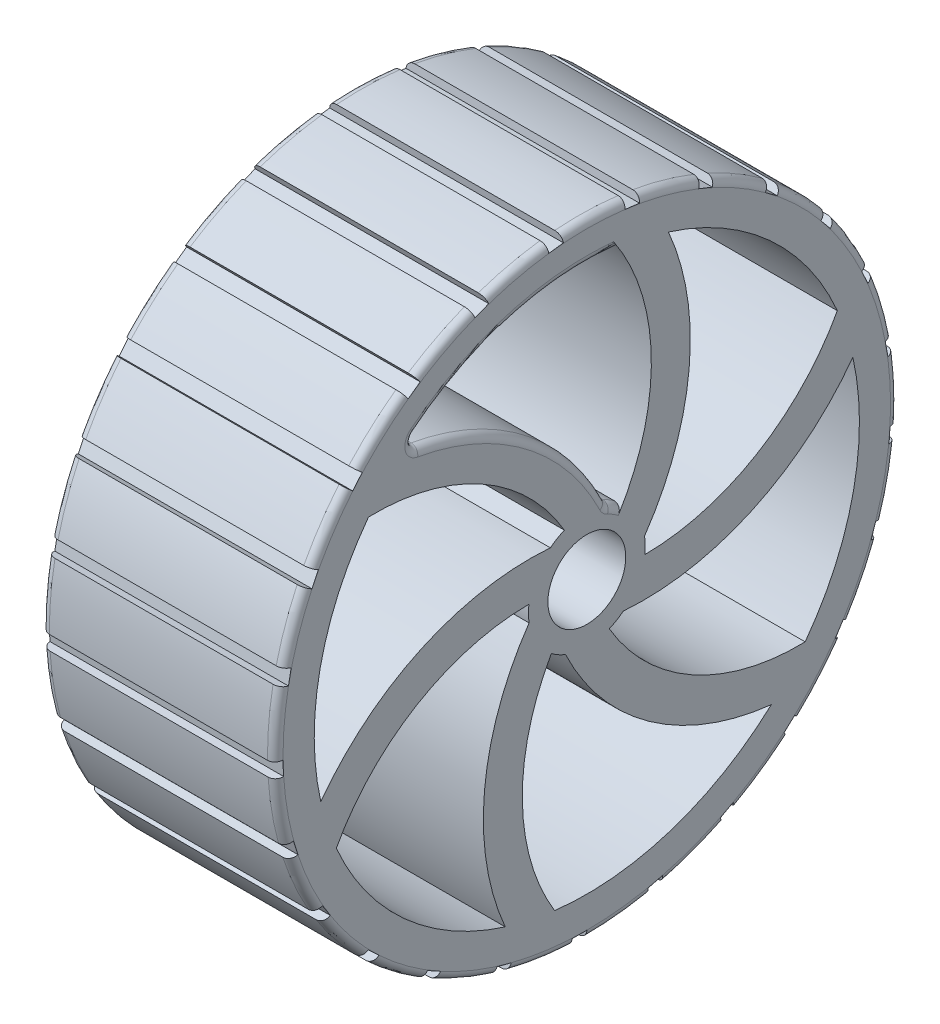
SolidWorks part; units mm, degrees
ref_plane "Front Plane" through (0, 0, 0) normal (0, 0, 1) x (1, 0, 0)
ref_plane "Top Plane" through (0, 0, 0) normal (0, 1, 0) x (1, 0, 0)
ref_plane "Right Plane" through (0, 0, 0) normal (1, 0, 0) x (0, 0, -1)
sketch "Sketch2" plane through (0, 0, 0) normal (1, 0, 0) x (0, 0, -1)
  circle A0 centre (0, 0) radius 101.6
  circle A1 centre (0, 0) radius 12.7
  circle A2 centre (0, 0) radius 19.05
  circle A3 centre (0, 0) radius 88.9
  arc A5 (18.8344, 2.8582) -> (26.5906, 84.8301) centre (-50.8, 50.8) ccw
  arc A7 (-18.8344, -2.8582) -> (-26.5906, -84.8301) centre (50.8, -50.8) ccw
  arc A9 (-18.8921, 2.4473) -> (-81.6973, -35.0537) centre (-18.5941, -69.3941) ccw
  arc A10 (7.3266, -17.5847) -> (71.206, -53.2251) centre (69.3941, 18.5941) ccw
  arc A11 (-11.8925, 14.8819) -> (-86.7603, -19.3869) centre (-18.5941, -69.3941) ccw
  arc A12 (-7.3266, 17.5847) -> (-71.206, 53.2251) centre (-69.3941, -18.5941) ccw
  arc A13 (6.9419, 17.7401) -> (-60.1697, 65.4432) centre (-69.3941, -18.5941) ccw
  arc A17 (-6.9419, -17.7401) -> (60.1697, -65.4432) centre (69.3941, 18.5941) ccw
  arc A18 (-11.5655, -15.1374) -> (-10.4913, -88.2788) centre (50.8, -50.8) ccw
  arc A20 (11.8925, -14.8819) -> (86.7603, 19.3869) centre (18.5941, 69.3941) ccw
  arc A21 (18.8921, -2.4473) -> (81.6973, 35.0537) centre (18.5941, 69.3941) ccw
  arc A28 (11.5655, 15.1374) -> (10.4913, 88.2788) centre (-50.8, 50.8) ccw
  point P42 (0, 0)
  dimension "D1" = 6.35
  dimension "D2" = 25.4
  dimension "D3" = 12.7
extrude "Boss-Extrude1" add sketch "Sketch2" along normal blind 76.2 contours A0 A3 | A28 A2 A5 A3 | A21 A2 A20 A3 | A2 A17 A3 A10 | A18 A2 A7 A3 | A2 A11 A3 A9 | A2 A13 A3 A12 | A2 A1 region at (0, 0, 98.7263) region at (0, -1.1915, -18.4728) region at (0, 48.0095, -24.0044) region at (0, 3.2163, -53.5797) region at (0, 44.7932, 29.5753) region at (0, -44.7932, -29.5753) region at (0, -3.2163, 53.5797) region at (0, -48.0095, 24.0044)
extrude "Boss-Extrude2" add sketch "Sketch2<3>" along normal blind 6.35 contours A1
sketch "Sketch2<3>" plane through (0, 0, 0) normal (1, 0, 0) x (0, 0, -1) same geometry as "Sketch2"
fillet "Fillet1" radius 2.54 31 edges at (76.2, 16.6005, -9.3448) (0, 16.6005, -9.3448) (76.2, 84.5923, 27.3378) (0, 84.5923, 27.3378) (38.1, 17.7401, -6.9419) (76.2, 50.314, 20.4141) (38.1, 65.4432, 60.1697) (0, 50.314, 20.4141) (0, 7.7113, -55.4249) (0, -7.4778, -53.7802) (0, -44.1438, -34.3906) (0, -50.314, -20.4141) (0, -51.8551, 21.0343) (0, -42.8361, 33.3661) (0, -7.7113, 55.4249) (0, 7.4778, 53.7802) (0, 44.1438, 34.3906) (0, 51.8551, -21.0343) (0, 42.8361, -33.3661) (0, -16.3931, -9.7041) (0, -18.621, -86.928) (0, -16.6005, 9.3448) (0, -84.5923, -27.3378) (0, -0.2075, 19.0489) (0, -65.9713, 59.5902) (0, 16.3931, 9.7041) (0, 18.621, 86.928) (0, 65.9713, -59.5902) (0, 0.2075, -19.0489) (0, 0, -101.6) (76.2, 0, -101.6)
sketch "Sketch3" plane through (0, 0, 0) normal (-1, 0, 0) x (0, 0, 1)
  line L1 (0, -99.06) -> (0, -107.5413)
  line L2 (0, -107.5413) -> (4.8174, -107.5413)
  line L3 (4.8174, -107.5413) -> (4.8174, -99.06)
  line L5 (0, -99.06) -> (4.8174, -99.06)
  line L6 (-26.7444, -104.1627) -> (-22.0784, -105.3607)
  line L7 (-22.0784, -105.3607) -> (-19.9692, -97.1459)
  line L8 (-24.6352, -95.9478) -> (-19.9692, -97.1459)
  line L9 (-24.6352, -95.9478) -> (-26.7444, -104.1627)
  line L10 (-51.8084, -94.2391) -> (-47.5869, -96.5599)
  line L11 (-47.5869, -96.5599) -> (-43.501, -89.1277)
  line L12 (-47.7225, -86.8069) -> (-43.501, -89.1277)
  line L13 (-47.7225, -86.8069) -> (-51.8084, -94.2391)
  line L14 (-73.6171, -78.3942) -> (-70.1053, -81.6919)
  line L15 (-70.1053, -81.6919) -> (-64.2995, -75.5094)
  line L16 (-67.8112, -72.2116) -> (-64.2995, -75.5094)
  line L17 (-67.8112, -72.2116) -> (-73.6171, -78.3942)
  line L18 (-90.8001, -57.6235) -> (-88.2188, -61.691)
  line L19 (-88.2188, -61.691) -> (-81.0578, -57.1465)
  line L20 (-83.6391, -53.079) -> (-81.0578, -57.1465)
  line L21 (-83.6391, -53.079) -> (-90.8001, -57.6235)
  line L22 (-102.2778, -33.2321) -> (-100.7892, -37.8137)
  line L23 (-100.7892, -37.8137) -> (-92.723, -35.1928)
  line L24 (-94.2117, -30.6112) -> (-92.723, -35.1928)
  line L25 (-94.2117, -30.6112) -> (-102.2778, -33.2321)
  line L26 (-107.3291, -6.7526) -> (-107.0266, -11.5605)
  line L27 (-107.0266, -11.5605) -> (-98.562, -11.0279)
  line L28 (-98.8645, -6.22) -> (-98.562, -11.0279)
  line L29 (-98.8645, -6.22) -> (-107.3291, -6.7526)
  line L30 (-105.6364, 20.1512) -> (-106.5391, 15.4192)
  line L31 (-106.5391, 15.4192) -> (-98.2081, 13.8299)
  line L32 (-97.3054, 18.562) -> (-98.2081, 13.8299)
  line L33 (-97.3054, 18.562) -> (-105.6364, 20.1512)
  line L34 (-97.3063, 45.7888) -> (-99.3574, 41.4299)
  line L35 (-99.3574, 41.4299) -> (-91.6833, 37.8188)
  line L36 (-89.6322, 42.1777) -> (-91.6833, 37.8188)
  line L37 (-89.6322, 42.1777) -> (-97.3063, 45.7888)
  line L38 (-82.862, 68.5494) -> (-85.9327, 64.8375)
  line L39 (-85.9327, 64.8375) -> (-79.3978, 59.4314)
  line L40 (-76.327, 63.1432) -> (-79.3978, 59.4314)
  line L41 (-76.327, 63.1432) -> (-82.862, 68.5494)
  line L42 (-63.2112, 87.0027) -> (-67.1085, 84.1711)
  line L43 (-67.1085, 84.1711) -> (-62.1234, 77.3096)
  line L44 (-58.226, 80.1412) -> (-62.1234, 77.3096)
  line L45 (-58.226, 80.1412) -> (-63.2112, 87.0027)
  line L46 (-39.5886, 99.9893) -> (-44.0677, 98.2159)
  line L47 (-44.0677, 98.2159) -> (-40.9455, 90.3303)
  line L48 (-36.4664, 92.1037) -> (-40.9455, 90.3303)
  line L49 (-36.4664, 92.1037) -> (-39.5886, 99.9893)
  line L50 (-13.4785, 106.6933) -> (-18.2579, 106.0895)
  line L51 (-18.2579, 106.0895) -> (-17.1949, 97.6751)
  line L52 (-12.4155, 98.2789) -> (-17.1949, 97.6751)
  line L53 (-12.4155, 98.2789) -> (-13.4785, 106.6933)
  line L54 (13.4785, 106.6933) -> (8.6991, 107.2971)
  line L55 (8.6991, 107.2971) -> (7.6361, 98.8827)
  line L56 (12.4155, 98.2789) -> (7.6361, 98.8827)
  line L57 (12.4155, 98.2789) -> (13.4785, 106.6933)
  line L58 (39.5886, 99.9893) -> (35.1095, 101.7627)
  line L59 (35.1095, 101.7627) -> (31.9873, 93.8771)
  line L60 (36.4664, 92.1037) -> (31.9873, 93.8771)
  line L61 (36.4664, 92.1037) -> (39.5886, 99.9893)
  line L62 (63.2112, 87.0027) -> (59.3138, 89.8343)
  line L63 (59.3138, 89.8343) -> (54.3287, 82.9728)
  line L64 (58.226, 80.1412) -> (54.3287, 82.9728)
  line L65 (58.226, 80.1412) -> (63.2112, 87.0027)
  line L66 (82.862, 68.5494) -> (79.7912, 72.2613)
  line L67 (79.7912, 72.2613) -> (73.2563, 66.8551)
  line L68 (76.327, 63.1432) -> (73.2563, 66.8551)
  line L69 (76.327, 63.1432) -> (82.862, 68.5494)
  line L70 (97.3063, 45.7888) -> (95.2551, 50.1478)
  line L71 (95.2551, 50.1478) -> (87.581, 46.5366)
  line L72 (89.6322, 42.1777) -> (87.581, 46.5366)
  line L73 (89.6322, 42.1777) -> (97.3063, 45.7888)
  line L74 (105.6364, 20.1512) -> (104.7337, 24.8833)
  line L75 (104.7337, 24.8833) -> (96.4027, 23.2941)
  line L76 (97.3054, 18.562) -> (96.4027, 23.2941)
  line L77 (97.3054, 18.562) -> (105.6364, 20.1512)
  line L78 (107.3291, -6.7526) -> (107.6315, -1.9447)
  line L79 (107.6315, -1.9447) -> (99.167, -1.4121)
  line L80 (98.8645, -6.22) -> (99.167, -1.4121)
  line L81 (98.8645, -6.22) -> (107.3291, -6.7526)
  line L82 (102.2778, -33.2321) -> (103.7665, -28.6505)
  line L83 (103.7665, -28.6505) -> (95.7003, -26.0296)
  line L84 (94.2117, -30.6112) -> (95.7003, -26.0296)
  line L85 (94.2117, -30.6112) -> (102.2778, -33.2321)
  line L86 (90.8001, -57.6235) -> (93.3814, -53.556)
  line L87 (93.3814, -53.556) -> (86.2204, -49.0115)
  line L88 (83.6391, -53.079) -> (86.2204, -49.0115)
  line L89 (83.6391, -53.079) -> (90.8001, -57.6235)
  line L90 (73.6171, -78.3942) -> (77.1288, -75.0965)
  line L91 (77.1288, -75.0965) -> (71.323, -68.9139)
  line L92 (67.8112, -72.2116) -> (71.323, -68.9139)
  line L93 (67.8112, -72.2116) -> (73.6171, -78.3942)
  line L94 (51.8084, -94.2391) -> (56.0299, -91.9183)
  line L95 (56.0299, -91.9183) -> (51.944, -84.4861)
  line L96 (47.7225, -86.8069) -> (51.944, -84.4861)
  line L97 (47.7225, -86.8069) -> (51.8084, -94.2391)
  line L98 (26.7444, -104.1627) -> (31.4105, -102.9646)
  line L99 (31.4105, -102.9646) -> (29.3013, -94.7498)
  line L100 (24.6352, -95.9478) -> (29.3013, -94.7498)
  line L101 (24.6352, -95.9478) -> (26.7444, -104.1627)
  circle A0 centre (0, 0) radius 101.6 construction
  circle A1 centre (0, 0) radius 99.06 construction
  point P108 (0, 0)
  dimension "D1" = 25
extrude "Cut-Extrude1" cut sketch "Sketch3" against normal blind 127
